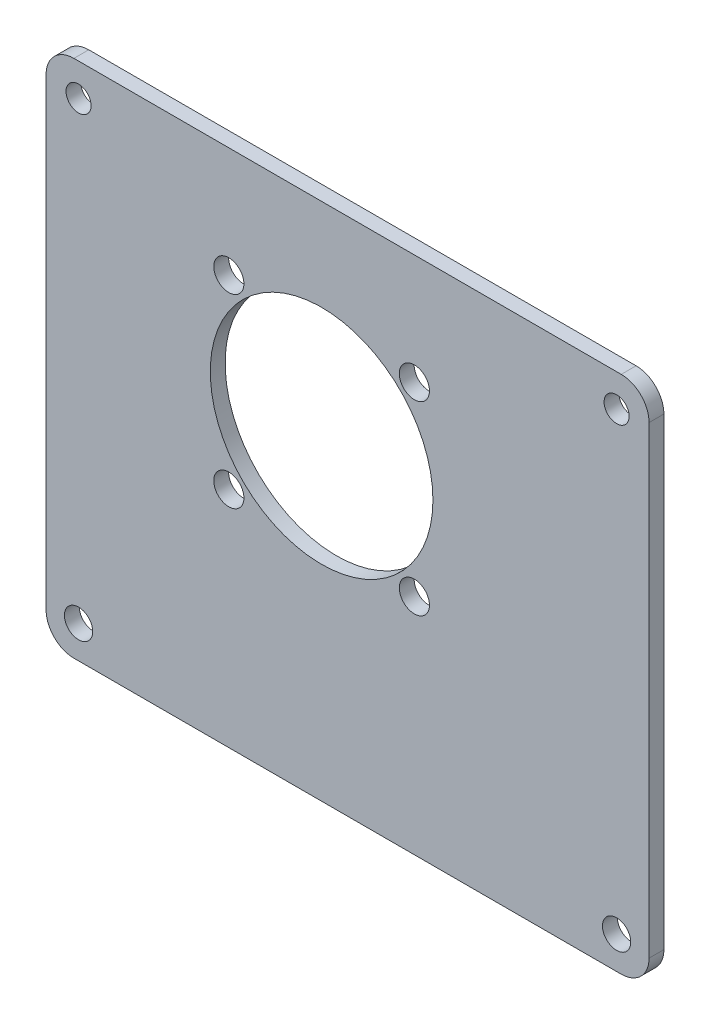
SolidWorks part; units mm, degrees
ref_plane "Front Plane" through (0, 0, 0) normal (0, 0, 1) x (1, 0, 0)
ref_plane "Top Plane" through (0, 0, 0) normal (0, 1, 0) x (1, 0, 0)
ref_plane "Right Plane" through (0, 0, 0) normal (1, 0, 0) x (0, 0, -1)
sketch "Sketch1" plane through (0, 0, 0) normal (0, 0, 1) x (1, 0, 0)
  line L0 (22.5, 25) -> (22.5, -25)
  line L1 (19, 24.5) -> (19.5, 25) construction
  line L2 (39.5, 28) -> (-39.5, 28) construction
  line L4 (42.5, -25) -> (42.5, 25)
  line L5 (39.5, 28) -> (-39.5, 28)
  line L6 (-42.5, 25) -> (-42.5, -25)
  line L7 (-39.5, -28) -> (39.5, -28)
  line L9 (19.5, 28) -> (-39.5, 28)
  line L10 (-42.5, 25) -> (-42.5, -25)
  line L11 (-39.5, -28) -> (19.5, -28)
  arc A0 (22.5, 25) -> (19.5, 28) centre (19.5, 25) ccw
  arc A1 (22.5, -25) -> (19.5, -28) centre (19.5, -25) cw
  circle A2 centre (19, 24.5) radius 1.35 construction
  circle A3 centre (-39, 24.5) radius 1.35 construction
  arc A4 (42.5, 25) -> (39.5, 28) centre (39.5, 25) ccw
  arc A5 (-39.5, 28) -> (-42.5, 25) centre (-39.5, 25) ccw
  arc A6 (-42.5, -25) -> (-39.5, -28) centre (-39.5, -25) ccw
  arc A7 (39.5, -28) -> (42.5, -25) centre (39.5, -25) ccw
  arc A9 (-39.5, 28) -> (-42.5, 25) centre (-39.5, 25) ccw
  arc A10 (-42.5, -25) -> (-39.5, -28) centre (-39.5, -25) ccw
  circle A11 centre (-39, -24.5) radius 1.524 construction
  circle A12 centre (19, -24.5) radius 1.524 construction
  circle A13 centre (-39, 24.5) radius 1.35
  circle A14 centre (-39, -24.5) radius 1.524
  circle A15 centre (19, -24.5) radius 1.524
  circle A16 centre (19, 24.5) radius 1.35
  point P18 (19, 24.5)
  dimension "D2" = 45
  dimension "D1" = 0
extrude "Boss-Extrude1" add sketch "Sketch1" along normal blind 1.6
sketch "Sketch2" plane through (0, 0, 1.6) normal (0, 0, 1) x (1, 0, 0)
  circle A0 centre (-2.7999, 16.11) radius 1.625
  circle A1 centre (-22.7999, 16.11) radius 1.625
  circle A2 centre (-22.7999, -3.89) radius 1.625
  circle A3 centre (-2.7999, -3.89) radius 1.625
  circle A4 centre (-12.7999, 6.11) radius 12
  dimension "D1" = 3.25
  dimension "D2" = 24
extrude "Cut-Extrude1" cut sketch "Sketch2" against normal through all
